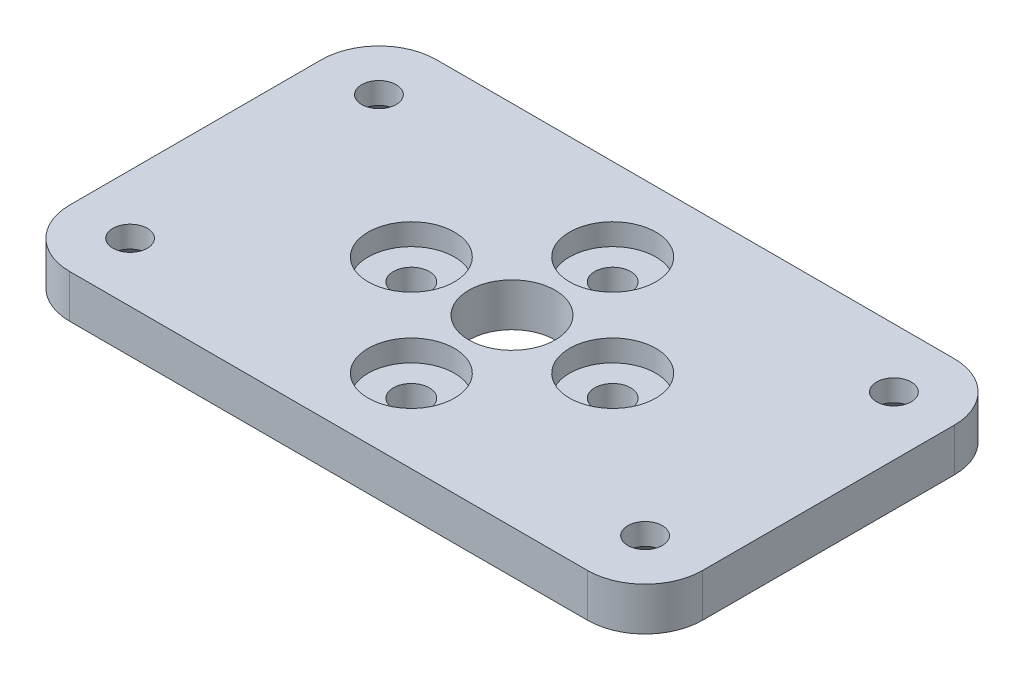
SolidWorks part; units mm, degrees
ref_plane "前视基准面" through (0, 0, 0) normal (0, 0, 1) x (1, 0, 0)
ref_plane "上视基准面" through (0, 0, 0) normal (0, 1, 0) x (1, 0, 0)
ref_plane "右视基准面" through (0, 0, 0) normal (1, 0, 0) x (0, 0, -1)
other "Configuration Table"
sketch "草图1" plane through (0, 0, 0) normal (0, 1, 0) x (1, 0, 0)
  line L0 (-13.2993, 0) -> (13.5934, 0) construction
  line L1 (0, 16.6571) -> (0, -12.7411) construction
  line L3 (22, -12.75) -> (-22, -12.75)
  line L4 (22, -12.75) -> (22, 12.75)
  line L5 (22, 12.75) -> (-22, 12.75)
  line L6 (-22, -12.75) -> (-22, 12.75)
  line L7 (22, -12.75) -> (-22, 12.75) construction
  line L8 (22, 12.75) -> (-22, -12.75) construction
  circle A0 centre (0, 0) radius 7 construction
  circle A1 centre (7, 0) radius 1.25
  circle A2 centre (0, -7) radius 1.25
  circle A3 centre (-7, 0) radius 1.25
  circle A4 centre (0, 7) radius 1.25
  circle A5 centre (-17.9, 8.65) radius 1.2
  circle A6 centre (17.9, 8.65) radius 1.2
  circle A7 centre (-17.9, -8.65) radius 1.2
  circle A8 centre (17.9, -8.65) radius 1.2
  circle A9 centre (0, 0) radius 3
  point P18 (0, 0)
  dimension "D1" = 14
  dimension "D2" = 2.5
  dimension "D4" = 35.8
  dimension "D5" = 17.3
  dimension "D6" = 2.4
  dimension "D7" = 44
  dimension "D8" = 25.5
  dimension "D3" = 4
extrude "凸台-拉伸1" add sketch "草图1" along normal blind 3
fillet "圆角1" radius 4 4 edges at (-22, 1.5, -12.75) (-22, 1.5, 12.75) (22, 1.5, 12.75) (22, 1.5, -12.75)
sketch "草图2" plane through (0, 3, 0) normal (0, 1, 0) x (1, 0, 0)
  circle A0 centre (7, 0) radius 3
  circle A1 centre (0, -7) radius 3
  circle A2 centre (-7, 0) radius 3
  circle A3 centre (0, 7) radius 3
  point P12 (0, 0)
  dimension "D1" = 6
  dimension "D2" = 4
extrude "切除-拉伸1" cut sketch "草图2" against normal blind 1.5
chamfer "倒角1" distance 1.5 angle 45 4 edges at (17.9, 0, -9.85) (17.9, 0, 9.85) (-17.9, 0, 7.45) (-17.9, 0, -7.45)
